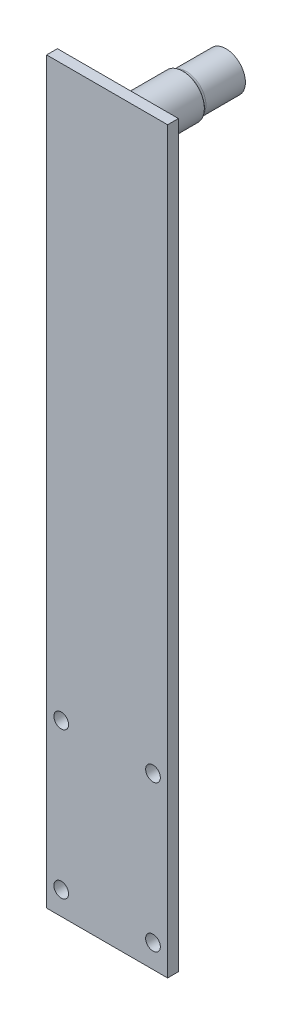
SolidWorks part; units mm, degrees
ref_plane "前视基准面" through (0, 0, 0) normal (0, 0, 1) x (1, 0, 0)
ref_plane "上视基准面" through (0, 0, 0) normal (0, 1, 0) x (1, 0, 0)
ref_plane "右视基准面" through (0, 0, 0) normal (1, 0, 0) x (0, 0, -1)
sketch "草图1" plane through (0, 0, 0) normal (0, 0, 1) x (1, 0, 0)
  line L1 (0, 0) -> (56, 0)
  line L2 (0, 0) -> (0, -89.4)
  line L3 (0, -89.4) -> (56, -89.4)
  line L4 (56, 0) -> (56, -89.4)
  dimension "D1" = 56
  dimension "D2" = 89.4
extrude "凸台-拉伸1" add sketch "草图1" along normal blind 5
sketch "草图5" plane through (0, 0, 5) normal (0, 0, 1) x (1, 0, 0)
  line L0 (56, 0) -> (49.234, -10.8014) construction
  line L1 (0, 0) -> (6.766, -10.8014) construction
  line L2 (49.234, -78.5986) -> (56, -89.4) construction
  line L3 (6.766, -78.5986) -> (0, -89.4) construction
  point P9 (49.234, -10.8014)
  point P10 (6.766, -10.8014)
  point P11 (6.766, -78.5986)
  point P12 (49.234, -78.5986)
hole_wizard "M8 螺纹孔2" positions "草图5" profile "草图6" tap size "M8" standard "GB"
sketch "草图6" plane through (49.234, -78.5986, 5) normal (1, 0, 0) x (0, -1, 0)
  line L0 (0, 0) -> (0, 21.7929)
  line L1 (0, 21.7929) -> (3.4, 19.75)
  line L2 (3.4, 19.75) -> (3.4, 0)
  line L5 (3.4, 0) -> (0, 0)
  line L10 (0, 21.7929) -> (-3.4, 19.75) construction
  line L11 (0, -6.35) -> (0, 107.95) construction
  dimension "螺纹孔钻头直径" = 6.8
  dimension "螺纹孔钻头深度" = 19.75
  dimension "导头角度" = 118
cosmetic thread "孔螺纹线5" parameters "D1"=16, "D2"=8
cosmetic thread "孔螺纹线6" parameters "D1"=16, "D2"=8
cosmetic thread "孔螺纹线7" parameters "D1"=16, "D2"=8
cosmetic thread "孔螺纹线8" parameters "D1"=16, "D2"=8
sketch "草图7" plane through (0, 0, 0) normal (0, 1, 0) x (1, 0, 0)
  line L1 (0, 0) -> (56, 0)
  line L2 (0, 0) -> (0, -5)
  line L3 (0, -5) -> (56, -5)
  line L4 (56, 0) -> (56, -5)
extrude "凸台-拉伸2" add sketch "草图7" along normal blind 252.5709
sketch "草图8" plane through (0, 0, 0) normal (0, 0, -1) x (-1, 0, 0)
  circle A0 centre (-28, 232.5709) radius 10
  dimension "D2" = 20
extrude "凸台-拉伸3" add sketch "草图8" along normal blind 30
sketch "草图9" plane through (0, 0, -30) normal (0, 0, -1) x (-1, 0, 0)
  circle A0 centre (-28, 232.5709) radius 9
  dimension "D1" = 18
extrude "凸台-拉伸4" add sketch "草图9" along normal blind 20
fillet "圆角1" radius 2 1 edges at (19, 232.5709, -30)
sketch "草图10" plane through (0, 252.5709, 0) normal (0, 1, 0) x (1, 0, 0)
  circle A0 centre (28, 15) radius 9
  dimension "D1" = 18
extrude "凸台-拉伸5" add sketch "草图10" against normal blind 35 from offset 20 offset against normal yes
sketch "草图11" plane through (0, 197.5709, 0) normal (0, -1, 0) x (1, 0, 0)
  circle A0 centre (28, -15) radius 8
  dimension "D1" = 16
extrude "切除-拉伸1" cut sketch "草图11" against normal blind 40
sketch "草图12" plane through (0, 0, -50) normal (0, 0, -1) x (-1, 0, 0)
  circle A0 centre (-28, 232.5709) radius 8
  dimension "D1" = 16
extrude "切除-拉伸2" cut sketch "草图12" against normal blind 45
